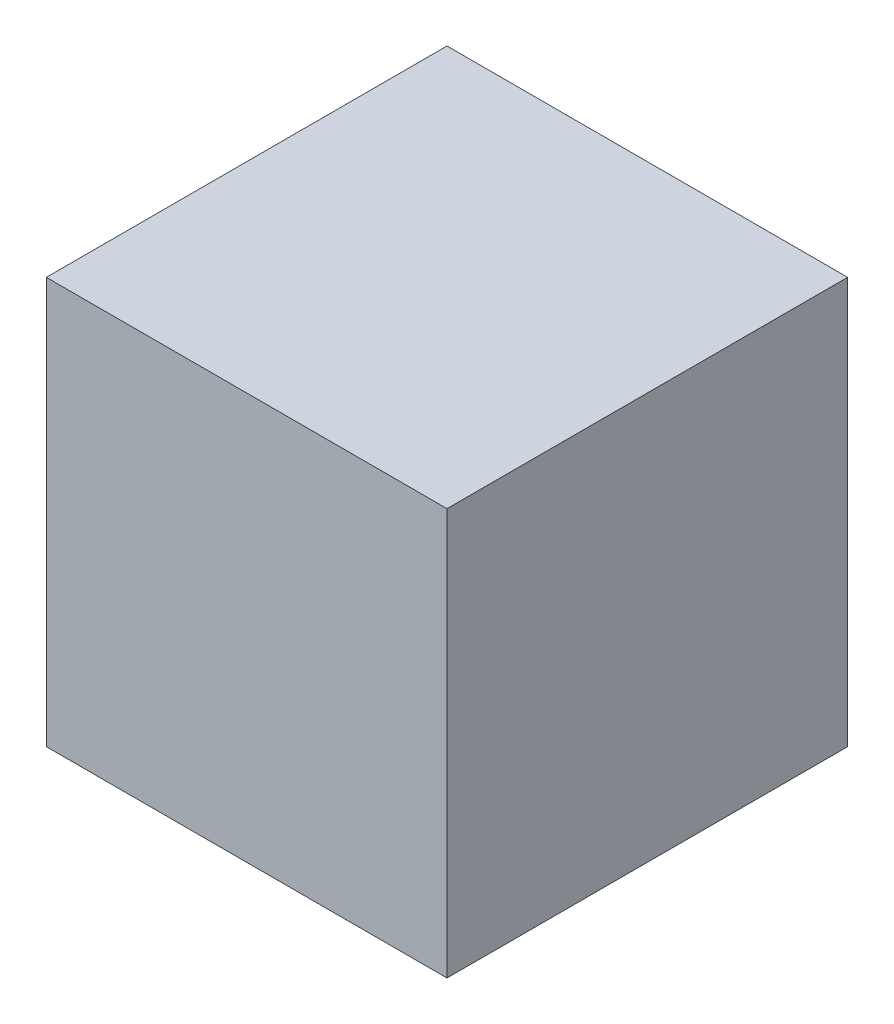
SolidWorks part; units mm, degrees
ref_plane "Front Plane" through (0, 0, 0) normal (0, 0, 1) x (1, 0, 0)
ref_plane "Top Plane" through (0, 0, 0) normal (0, 1, 0) x (1, 0, 0)
ref_plane "Right Plane" through (0, 0, 0) normal (1, 0, 0) x (0, 0, -1)
sketch "Sketch1" plane through (0, 0, 0) normal (0, 1, 0) x (1, 0, 0)
  line L1 (3.45, -3.45) -> (-3.45, -3.45)
  line L2 (3.45, -3.45) -> (3.45, 3.45)
  line L3 (3.45, 3.45) -> (-3.45, 3.45)
  line L4 (-3.45, -3.45) -> (-3.45, 3.45)
  line L5 (3.45, -3.45) -> (-3.45, 3.45) construction
  line L6 (3.45, 3.45) -> (-3.45, -3.45) construction
  point P0 (0, 0)
  dimension "D1" = 6.9
  dimension "D2" = 6.9
extrude "Boss-Extrude1" add sketch "Sketch1" along normal blind 7
sketch "Sketch2" plane through (0, 0, -3.45) normal (0, 0, -1) x (-1, 0, 0)
  line L0 (-3.45, 7) -> (3.45, 7) construction
  line L1 (-2.5, 6.5) -> (2.5, 6.5)
  line L2 (-2.5, 6.5) -> (-2.5, 2.5)
  line L3 (-2.5, 2.5) -> (2.5, 2.5)
  line L4 (2.5, 6.5) -> (2.5, 2.5)
  line L5 (-2.5, 6.5) -> (2.5, 2.5) construction
  line L6 (-2.5, 2.5) -> (2.5, 6.5) construction
  point P0 (0, 4.5)
  dimension "D1" = 5
  dimension "D2" = 4
  dimension "D3" = 0.5
extrude "Cut-Extrude1" cut sketch "Sketch2" against normal blind 2
